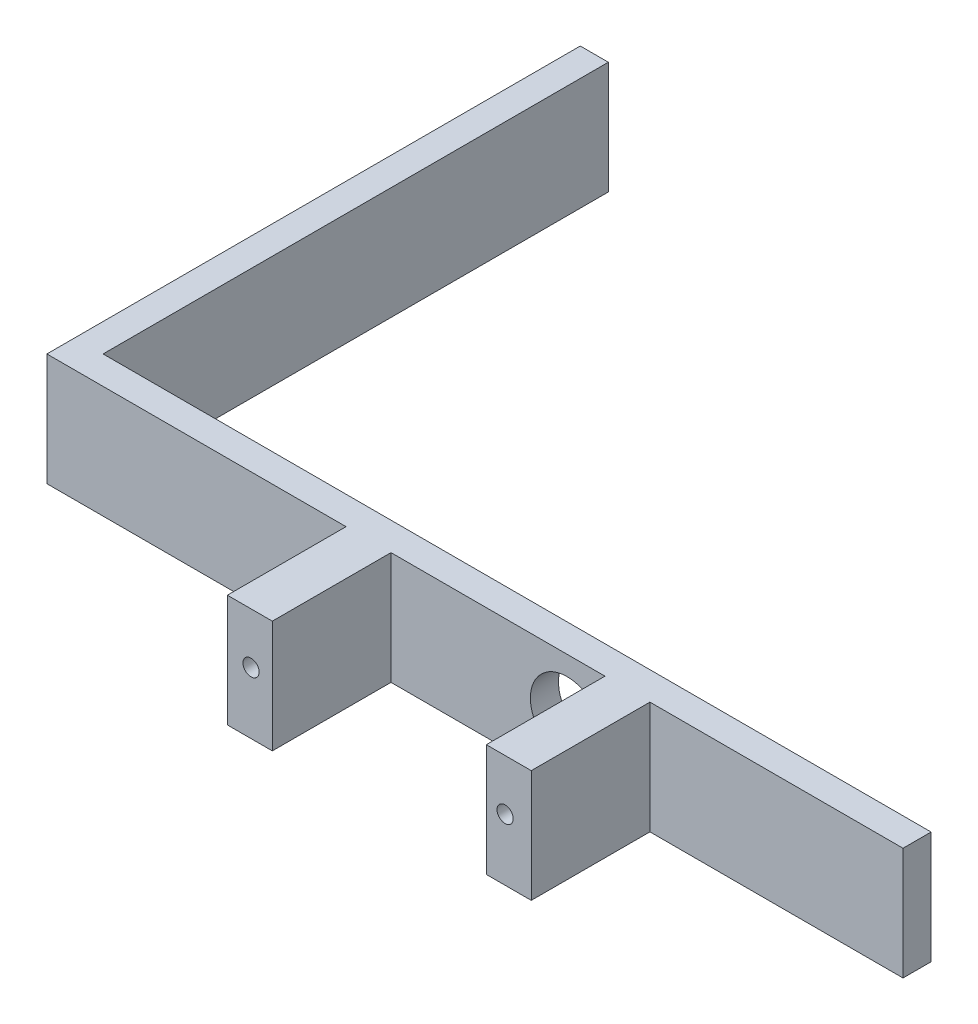
SolidWorks part; units mm, degrees
ref_plane "Front Plane" through (0, 0, 0) normal (0, 0, 1) x (1, 0, 0)
ref_plane "Top Plane" through (0, 0, 0) normal (0, 1, 0) x (1, 0, 0)
ref_plane "Right Plane" through (0, 0, 0) normal (1, 0, 0) x (0, 0, -1)
sketch "Sketch1" plane through (0, 0, 0) normal (0, 1, 0) x (1, 0, 0)
  line L1 (0, 0) -> (3.9688, 0)
  line L2 (0, 0) -> (0, 75.3427)
  line L3 (0, 75.3427) -> (3.9688, 75.3427)
  line L4 (3.9688, 3.9688) -> (3.9688, 75.3427)
  line L5 (3.9688, 0) -> (120.9358, 0)
  line L7 (3.9688, 3.9688) -> (120.9358, 3.9688)
  line L8 (120.9358, 0) -> (120.9358, 3.9688)
  dimension "D1" = 3.9688
  dimension "D2" = 3.9688
  dimension "D3" = 71.374
  dimension "D4" = 116.967
extrude "Boss-Extrude1" add sketch "Sketch1" along normal mid plane 15.875
sketch "Sketch2" plane through (0, 0, 0) normal (0, 0, 1) x (1, 0, 0)
  line L0 (120.9358, 7.9375) -> (120.9358, -7.9375) construction
  circle A0 centre (73.5013, 0) radius 5.207
  dimension "D1" = 47.4345
  dimension "D2" = 10.414
extrude "Cut-Extrude1" cut sketch "Sketch2" against normal up to surface (3.9688 mm away) up to face at (62.4522, 0, -3.9688)
sketch "Sketch4" plane through (0, 0, 0) normal (0, 0, 1) x (1, 0, 0)
  line L0 (0, -7.9375) -> (120.9358, -7.9375) construction
  line L1 (0, 7.9375) -> (120.9358, 7.9375) construction
  line L2 (42.2593, 7.9375) -> (48.6093, 7.9375)
  line L3 (42.2593, 7.9375) -> (42.2593, -7.9375)
  line L4 (42.2593, -7.9375) -> (48.6093, -7.9375)
  line L5 (48.6093, 7.9375) -> (48.6093, -7.9375)
  line L7 (78.8353, 7.9375) -> (85.1853, 7.9375)
  line L8 (78.8353, 7.9375) -> (78.8353, -7.9375)
  line L9 (78.8353, -7.9375) -> (85.1853, -7.9375)
  line L10 (85.1853, 7.9375) -> (85.1853, -7.9375)
  circle A0 centre (73.5013, 0) radius 5.207 construction
  dimension "D4" = 5.334
  dimension "D1" = 6.35
  dimension "D2" = 6.35
  dimension "D3" = 24.892
extrude "Boss-Extrude2" add sketch "Sketch4" along normal blind 16.764
sketch "Sketch6" plane through (0, 0, 16.764) normal (0, 0, 1) x (1, 0, 0)
  circle A0 centre (81.4926, 0.7617) radius 1.143
  circle A1 centre (45.6024, 0.7617) radius 1.143
  dimension "D1" = 2.286
  dimension "D2" = 2.286
extrude "Cut-Extrude2" cut sketch "Sketch6" against normal blind 12.7
